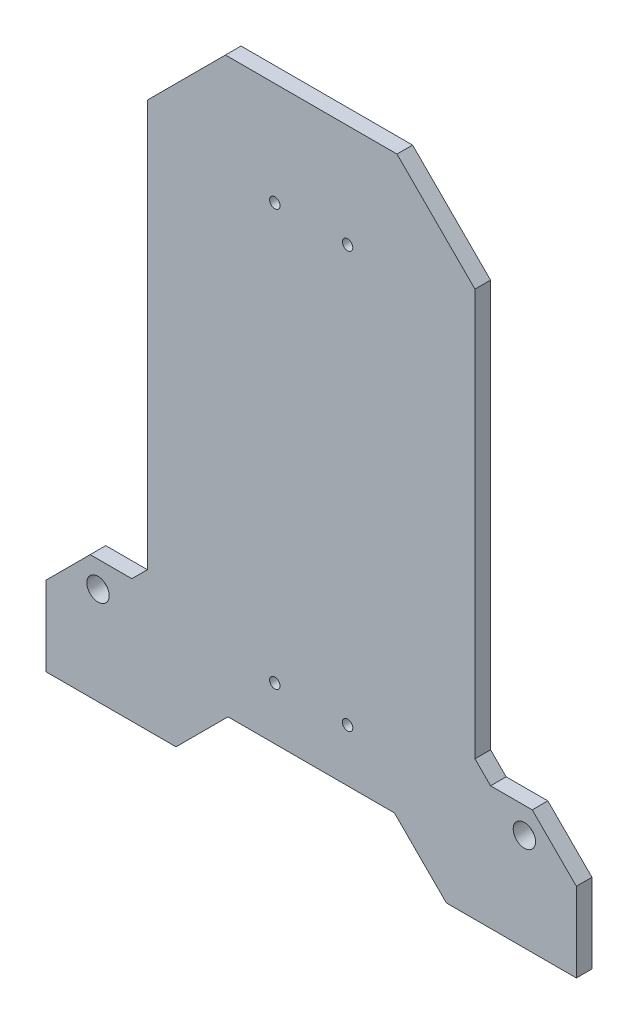
SolidWorks part; units mm, degrees
material "ABS"
ref_plane "前视基准面" through (0, 0, 0) normal (0, 0, 1) x (1, 0, 0)
ref_plane "上视基准面" through (0, 0, 0) normal (0, 1, 0) x (1, 0, 0)
ref_plane "右视基准面" through (0, 0, 0) normal (1, 0, 0) x (0, 0, -1)
sketch "草图1" plane through (0, 0, 0) normal (0, 0, 1) x (1, 0, 0)
  line L0 (-51.0025, -68.8919) -> (51.0025, -68.8919)
  line L1 (-51.0025, -141.1287) -> (-51.0025, -53.6128) construction
  line L2 (51.0025, -53.6128) -> (51.0025, -141.1287) construction
  line L3 (51.0025, -68.8919) -> (51.0025, 35.2667)
  line L5 (51.0025, 35.2667) -> (40.1096, 51.1081)
  line L6 (40.1096, 51.1081) -> (-37.0964, 51.1081)
  line L7 (-37.0964, 51.1081) -> (-51.0025, 41.546)
  line L8 (-51.0025, 41.546) -> (-51.0025, -68.8919)
  line L9 (53.9975, -68.8919) -> (-54.0025, -68.8919) construction
  dimension "D1" = 120
extrude "凸台-拉伸1" add sketch "草图1" against normal blind 3
sketch "草图2" plane through (0, 0, 0) normal (0, 0, 1) x (1, 0, 0)
  circle A0 centre (-41.0025, 9.8725) radius 2.15
  circle A1 centre (-41.0025, -50.1275) radius 2.15
  circle A2 centre (41.0025, 9.8725) radius 2.15
  circle A3 centre (41.0025, -50.1275) radius 2.15
extrude "切除-拉伸1" cut sketch "草图2" against normal blind 3
sketch "草图3" plane through (0, 0, -3) normal (0, 0, -1) x (-1, 0, 0)
  circle A0 centre (-7.0002, 31.25) radius 1
  circle A1 centre (6.9998, 31.25) radius 1
  circle A2 centre (-7.0002, -48.75) radius 1
  circle A3 centre (6.9998, -48.75) radius 1
extrude "切除-拉伸2" cut sketch "草图3" against normal blind 70
sketch "Sketch1" plane through (0, 0, 0) normal (0, 0, 1) x (1, 0, 0)
  line L0 (51.0025, -53.6128) -> (42.5172, -45.1275) construction
  line L1 (42.5172, -45.1275) -> (26.0025, -45.1275) construction
  line L2 (-26.0025, -45.1275) -> (-42.5172, -45.1275) construction
  line L3 (-42.5172, -45.1275) -> (-51.0025, -53.6128) construction
  line L4 (51.0025, -53.6128) -> (42.5172, -45.1275)
  line L5 (42.5172, -45.1275) -> (31.5, -45.1275)
  line L6 (-31.5, -45.1275) -> (-42.5172, -45.1275)
  line L7 (-42.5172, -45.1275) -> (-51.0025, -53.6128)
  line L8 (-31.5, 54.9564) -> (-31.5, -45.1275)
  line L9 (-31.5, -46.8213) -> (-31.5, 52.4522) construction
  line L10 (-37.0964, 51.1081) -> (-51.0025, 41.546) construction
  line L11 (31.5, 63.6291) -> (31.5, -45.1275)
  line L12 (31.5, 52.4522) -> (31.5, -46.8213) construction
  line L13 (51.0025, 35.2667) -> (40.1096, 51.1081) construction
  line L14 (-31.5, 54.9564) -> (-51.0025, 54.9564)
  line L15 (-51.0025, 54.9564) -> (-51.0025, -53.6128)
  line L16 (31.5, 63.6291) -> (51.0025, 63.6291)
  line L17 (51.0025, 63.6291) -> (51.0025, -53.6128)
extrude "Cut-Extrude1" cut sketch "Sketch1" against normal blind 10
chamfer "Chamfer1" distance 15 angle 45 2 edges at (-31.5, 51.1081, -1.5) (31.5, 51.1081, -1.5)
chamfer "Chamfer2" distance 3 angle 45 2 edges at (31.5, -45.1275, -1.5) (-31.5, -45.1275, -1.5)
sketch "Sketch2" plane through (0, 0, 0) normal (0, 0, 1) x (1, 0, 0)
  line L0 (-26.0025, -68.8919) -> (-16.0025, -58.8919)
  line L1 (-51.0025, -68.8919) -> (51.0025, -68.8919) construction
  line L2 (-16.0025, -58.8919) -> (16.0025, -58.8919)
  line L3 (16.0025, -58.8919) -> (26.0025, -68.8919)
  line L4 (26.0025, -68.8919) -> (-26.0025, -68.8919)
  line L5 (-51.0025, -53.6128) -> (-51.0025, -68.8919) construction
  dimension "D1" = 45
  dimension "D2" = 45
  dimension "D3" = 25
  dimension "D4" = 25
  dimension "D5" = 10
extrude "Cut-Extrude2" cut sketch "Sketch2" against normal blind 10
